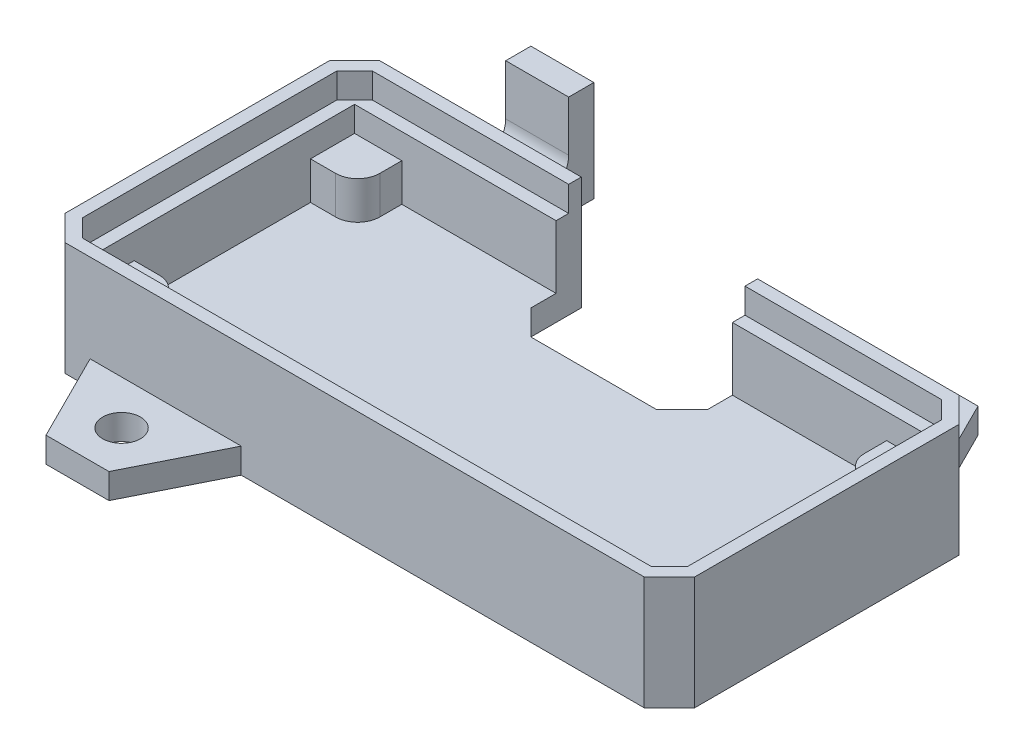
SolidWorks part; units mm, degrees
material "PLA+"
ref_plane "Front Plane" through (0, 0, 0) normal (0, 0, 1) x (1, 0, 0)
ref_plane "Top Plane" through (0, 0, 0) normal (0, 1, 0) x (1, 0, 0)
ref_plane "Right Plane" through (0, 0, 0) normal (1, 0, 0) x (0, 0, -1)
sketch "Sketch1" plane through (0, 0, 0) normal (0, 1, 0) x (1, 0, 0)
  line L0 (-7, 12.5) -> (-23, 12.5)
  line L1 (23, 12.5) -> (7, 12.5)
  line L2 (25, 10.5) -> (25, -10.5)
  line L3 (23, -12.5) -> (-23, -12.5)
  line L4 (-25, 10.5) -> (-25, -10.5)
  line L5 (25, 12.5) -> (-25, -12.5) construction
  line L6 (25, -12.5) -> (-25, 12.5) construction
  line L7 (0, 0) -> (0, 11.0838) construction
  line L8 (-7, 12.5) -> (-7, 8.5)
  line L9 (-5, 6.5) -> (5, 6.5)
  line L10 (7, 12.5) -> (7, 8.5)
  line L11 (-23, 12.5) -> (-25, 10.5)
  line L12 (25, 10.5) -> (23, 12.5)
  line L13 (25, -10.5) -> (23, -12.5)
  line L14 (-23, -12.5) -> (-25, -10.5)
  line L15 (-7, 8.5) -> (-5, 6.5)
  line L16 (5, 6.5) -> (7, 8.5)
  point P0 (0, 0)
  point P7 (7, 6.5)
  point P8 (-7, 6.5)
  dimension "D1" = 50
  dimension "D2" = 25
  dimension "D3" = 14
  dimension "D4" = 6
extrude "Boss-Extrude1" add sketch "Sketch1" along normal blind 2
sketch "Sketch2" plane through (0, 2, 0) normal (0, 1, 0) x (1, 0, 0)
  line L0 (7, 12.5) -> (23, 12.5)
  line L1 (25, 10.5) -> (25, -10.5)
  line L2 (0, 0) -> (2.9968, 0) construction
  line L3 (23, -12.5) -> (0, -12.5)
  line L4 (-23, -12.5) -> (23, -12.5) construction
  line L5 (7, 10.5) -> (23, 10.5)
  line L6 (23, 10.5) -> (23, -10.5)
  line L7 (23, -10.5) -> (0, -10.5)
  line L8 (19.25, 8.75) -> (19.25, 10.5)
  line L9 (21, 7) -> (23, 7)
  line L10 (21, -7) -> (23, -7)
  line L11 (19.25, -8.75) -> (19.25, -10.5)
  line L12 (7, 10.5) -> (7, 12.5)
  line L13 (23, 12.5) -> (25, 10.5)
  line L14 (0, 0) -> (0, 2.3496) construction
  line L15 (-19.25, -8.75) -> (-19.25, -10.5)
  line L16 (-21, -7) -> (-23, -7)
  line L17 (-23, -10.5) -> (0, -10.5)
  line L18 (-23, -12.5) -> (0, -12.5)
  line L19 (-21, 7) -> (-23, 7)
  line L20 (-19.25, 8.75) -> (-19.25, 10.5)
  line L21 (-23, 10.5) -> (-23, -10.5)
  line L22 (-25, 10.5) -> (-25, -10.5)
  line L23 (-7, 10.5) -> (-7, 12.5)
  line L24 (-7, 10.5) -> (-23, 10.5)
  line L25 (-7, 12.5) -> (-23, 12.5)
  line L26 (7, 12.5) -> (25, 12.5) construction
  line L27 (25, 12.5) -> (25, -12.5) construction
  line L28 (23, -12.5) -> (25, -10.5)
  line L29 (25, -12.5) -> (0, -12.5) construction
  line L30 (-25, -10.5) -> (-23, -12.5)
  line L31 (-25, 10.5) -> (-23, 12.5)
  line L39 (7, 10.5) -> (23, 10.5) construction
  line L40 (23, 10.5) -> (23, -10.5) construction
  line L42 (23, -10.5) -> (0, -10.5) construction
  arc A0 (-21, -7) -> (-19.25, -8.75) centre (-21, -8.75) cw
  arc A1 (21, -7) -> (19.25, -8.75) centre (21, -8.75) ccw
  arc A2 (19.25, 8.75) -> (21, 7) centre (21, 8.75) ccw
  arc A3 (-19.25, 8.75) -> (-21, 7) centre (-21, 8.75) cw
  line M2 (-25, 10.5) -> (-25, -10.5)
  line M3 (-23, -12.5) -> (23, -12.5)
  line M4 (25, -10.5) -> (25, 10.5)
  line M5 (23, 12.5) -> (7, 12.5)
  line M6 (7, 12.5) -> (7, 8.5)
  line M8 (-7, 8.5) -> (-7, 12.5)
  line M9 (-7, 12.5) -> (-23, 12.5)
  dimension "D1" = 3.5
  dimension "D3" = 21
  dimension "D4" = 2
  dimension "D6" = 17.5
  dimension "D9" = 2
extrude "PcbLedge" add sketch "Sketch2" along normal blind 3 contours L10 A1 L11 L7 L6 | L8 A2 L9 L6 L5 | A3 L20 L24 L21 L19 | A0 L16 L21 L17 L15 region at (21.2032, 2, -8.8216) region at (21.2032, 2, 8.8216) region at (-21.2032, 2, 8.8216) region at (-21.2032, 2, -8.8216)
extrude "Boss-Extrude3" add sketch "Sketch2<3>" along normal blind 5 contours L24 L5 L6 L7 L17 L21 M8 M9 M2 M3 M4 M5 M6 region at (15, 2, -11.941)
sketch "Sketch2<3>" plane through (0, 2, 0) normal (0, 1, 0) x (1, 0, 0) same geometry as "Sketch2"
sketch "Sketch4" plane through (0, 0, 0) normal (0, -1, 0) x (1, 0, 0)
  line L0 (21, -12.5) -> (17.5, -19.5)
  line L1 (23, -12.5) -> (7, -12.5) construction
  line L2 (17.5, -19.5) -> (12.5, -19.5)
  line L3 (12.5, -19.5) -> (9, -12.5)
  line L4 (9, -12.5) -> (21, -12.5)
  line L5 (9, -12.5) -> (0, 0) construction
  line L6 (0, 0) -> (-10.2661, 14.2585) construction
  line L7 (-12.5, 19.5) -> (-9, 12.5)
  line L8 (-9, 12.5) -> (-21, 12.5)
  line L9 (23, -12.5) -> (7, -12.5) construction
  line L10 (7, -12.5) -> (7, -10.5) construction
  line L11 (-23, 12.5) -> (23, 12.5) construction
  line L14 (-21, 12.5) -> (-17.5, 19.5)
  line L15 (-17.5, 19.5) -> (-12.5, 19.5)
  circle A0 centre (15, -16) radius 1.5
  circle A1 centre (-15, 16) radius 1.5
  point P27 (15, -12.5)
  point P30 (15, -19.5)
  point P37 (-15, 19.5)
  dimension "D4" = 3.5
  dimension "D8" = 3.5
  dimension "D5" = 3
  dimension "D11" = 8
  dimension "D2" = 12
  dimension "D3" = 7
  dimension "D6" = 7
  dimension "D7" = 5
  dimension "D9" = 12
  dimension "D10" = 5
extrude "ForScrews" add sketch "Sketch4" against normal blind 2
sketch "Sketch5" plane through (0, 7, 0) normal (0, 1, 0) x (1, 0, 0)
  line L0 (23, 12.5) -> (7, 12.5) construction
  line L1 (25, 10.5) -> (23, 12.5) construction
  line L2 (25, -10.5) -> (25, 10.5) construction
  line L3 (23, -12.5) -> (25, -10.5) construction
  line L4 (-23, -12.5) -> (23, -12.5) construction
  line L5 (-25, -10.5) -> (-23, -12.5) construction
  line L6 (-25, 10.5) -> (-25, -10.5) construction
  line L7 (-23, 12.5) -> (-25, 10.5) construction
  line L8 (-7, 12.5) -> (-23, 12.5) construction
  line L9 (23, 12.5) -> (7, 12.5)
  line L10 (25, 10.5) -> (23, 12.5)
  line L11 (25, -10.5) -> (25, 10.5)
  line L12 (23, -12.5) -> (25, -10.5)
  line L13 (-23, -12.5) -> (23, -12.5)
  line L14 (-25, -10.5) -> (-23, -12.5)
  line L15 (-25, 10.5) -> (-25, -10.5)
  line L16 (-23, 12.5) -> (-25, 10.5)
  line L17 (-7, 12.5) -> (-23, 12.5)
  line L18 (-7, 11.5) -> (-22.5858, 11.5)
  line L19 (-22.5858, 11.5) -> (-24, 10.0858)
  line L20 (-24, 10.0858) -> (-24, -10.0858)
  line L21 (-24, -10.0858) -> (-22.5858, -11.5)
  line L22 (-22.5858, -11.5) -> (22.5858, -11.5)
  line L23 (22.5858, -11.5) -> (24, -10.0858)
  line L24 (24, -10.0858) -> (24, 10.0858)
  line L25 (24, 10.0858) -> (22.5858, 11.5)
  line L26 (22.5858, 11.5) -> (7, 11.5)
  line L27 (-7, 12.5) -> (-7, 11.5)
  line L29 (7, 12.5) -> (7, 11.5)
  line M5 (-7, 10.5) -> (-7, 12.5)
  line M6 (-7, 12.5) -> (-23, 12.5)
  line M7 (-23, 12.5) -> (-25, 10.5)
  line M8 (-25, 10.5) -> (-25, -10.5)
  line M9 (-25, -10.5) -> (-23, -12.5)
  line M10 (-23, -12.5) -> (23, -12.5)
  line M11 (23, -12.5) -> (25, -10.5)
  line M12 (25, -10.5) -> (25, 10.5)
  line M13 (25, 10.5) -> (23, 12.5)
  line M14 (23, 12.5) -> (7, 12.5)
  line M15 (7, 12.5) -> (7, 10.5)
  dimension "D1" = 1
extrude "Groove" add sketch "Sketch5" along normal blind 2 contours L26 L25 L24 L23 L22 L21 L20 L19 L18 M5 M6 M7 M8 M9 M10 M11 M12 M13 M14 M15 region at (23.6047, 7, -11.1047)
sketch "Sketch6" plane through (0, 0, 0) normal (0, -1, 0) x (1, 0, 0)
  line L0 (-7, -12.5) -> (-23, -12.5) construction
  line L1 (-19, -12.5) -> (-14, -12.5)
  line L2 (-19, -12.5) -> (-19, -20.5)
  line L3 (-19, -20.5) -> (-14, -20.5)
  line L4 (-14, -12.5) -> (-14, -20.5)
  dimension "D1" = 5
  dimension "D2" = 8
  dimension "D3" = 4
extrude "Boss-Extrude6" add sketch "Sketch6" against normal blind 8
sketch "Sketch7" plane through (-19, 0, 0) normal (-1, 0, 0) x (0, 0, 1)
  line L0 (-12.5, 9) -> (-12.5, 0) construction
  line L1 (-12.5, 0) -> (-20.5, 0) construction
  line L2 (-16.5, 2) -> (-12.5, 2)
  line L3 (-12.5, 2) -> (-12.5, 8.7284)
  line L4 (-12.5, 8.7284) -> (-18.5, 8.7284)
  line L5 (-18.5, 8.7284) -> (-18.5, 4)
  line L6 (-20.5, 8) -> (-20.5, 0) construction
  arc A0 (-18.5, 4) -> (-16.5, 2) centre (-16.5, 4) ccw
  dimension "D1" = 2
  dimension "D2" = 4
  dimension "D3" = 2
extrude "Cut-Extrude1" cut sketch "Sketch7" against normal blind 7
sketch3d "CableAxis"
  line L0 (-19, 4, -16.5) -> (-14, 4, -16.5) construction
  line L1 (-14, 2, -16.5) -> (-19, 2, -16.5) construction
